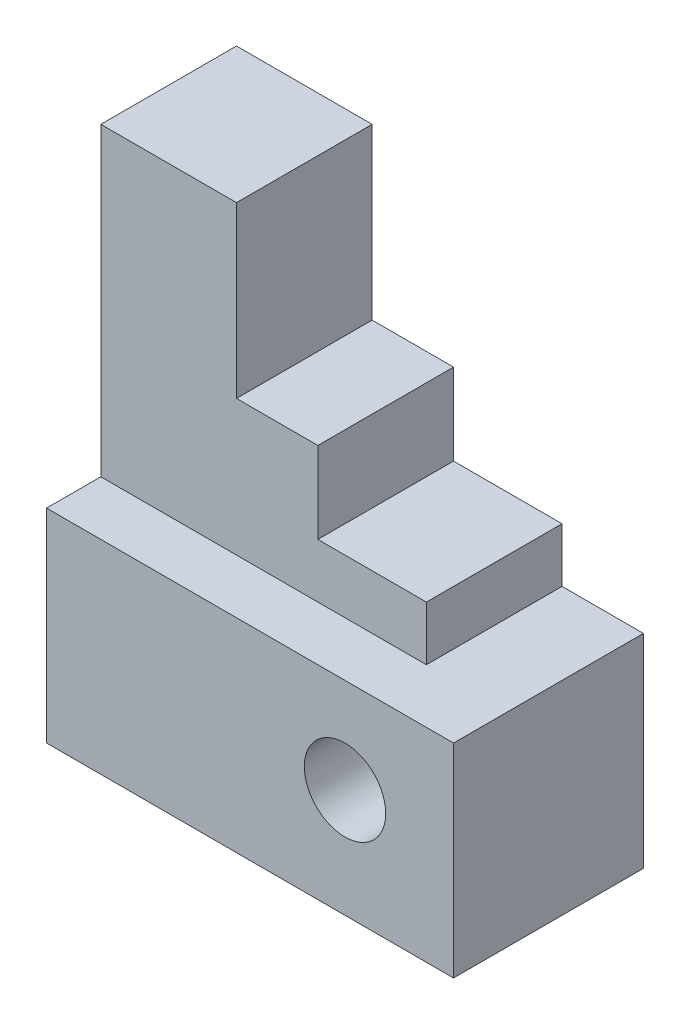
SolidWorks part; units mm, degrees
ref_plane "Front Plane" through (0, 0, 0) normal (0, 0, 1) x (1, 0, 0)
ref_plane "Top Plane" through (0, 0, 0) normal (0, 1, 0) x (1, 0, 0)
ref_plane "Right Plane" through (0, 0, 0) normal (1, 0, 0) x (0, 0, -1)
sketch "Sketch8" plane through (0, 0, 0) normal (0, 0, 1) x (1, 0, 0)
  line L0 (0, 0) -> (60, 0)
  line L1 (60, 0) -> (60, 30)
  line L2 (60, 30) -> (0, 30)
  line L3 (0, 30) -> (0, 0)
  line L4 (0, 30) -> (0, 75)
  line L5 (0, 75) -> (20, 75)
  line L6 (20, 75) -> (20, 50)
  line L7 (20, 50) -> (32, 50)
  line L8 (32, 50) -> (32, 38)
  line L9 (32, 38) -> (48, 38)
  line L10 (48, 38) -> (48, 30)
  circle A0 centre (44, 16) radius 6
  dimension "D6" = 12
  dimension "D1" = 60
  dimension "D2" = 75
  dimension "D3" = 16
  dimension "D4" = 30
  dimension "D5" = 16
  dimension "D7" = 12
  dimension "D8" = 20
  dimension "D9" = 20
  dimension "D10" = 12
  dimension "D11" = 12
extrude "Boss-Extrude5" add sketch "Sketch8" along normal blind 28 separate body contours L2 L3 L0 L1 A0 region at (29.0614, 14.933, 0)
extrude "Boss-Extrude6" add sketch "Sketch8<3>" along normal blind 20 contours L10 L9 L8 L7 L6 L5 L4 L2 region at (16.0568, 48.2666, 0)
sketch "Sketch8<3>" plane through (0, 0, 0) normal (0, 0, 1) x (1, 0, 0) same geometry as "Sketch8"
